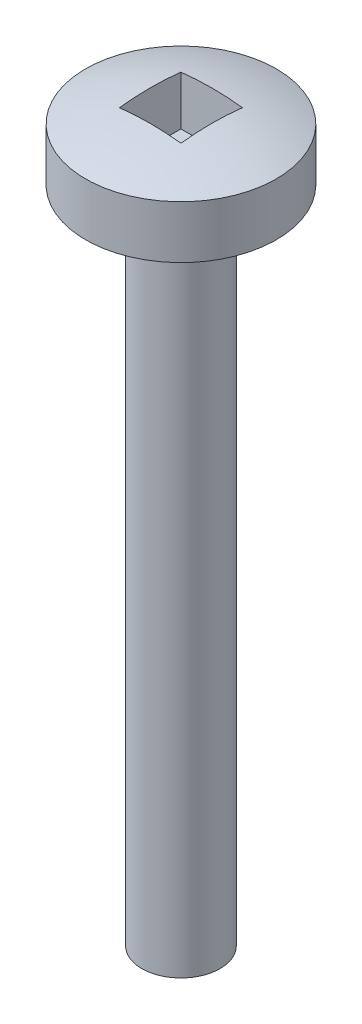
SolidWorks part; units mm, degrees
material "Cast Alloy Steel"
ref_plane "Front Plane" through (0, 0, 0) normal (0, 0, 1) x (1, 0, 0)
ref_plane "Top Plane" through (0, 0, 0) normal (0, 1, 0) x (1, 0, 0)
ref_plane "Right Plane" through (0, 0, 0) normal (1, 0, 0) x (0, 0, -1)
sketch "Sketch1" plane through (0, 0, 0) normal (0, 1, 0) x (1, 0, 0)
  circle A0 centre (0, 0) radius 1.1303
  dimension "D1" = 2.2606
extrude "threads" add sketch "Sketch1" against normal blind 19.05
sketch "Sketch2" plane through (0, 0, 0) normal (0, 1, 0) x (1, 0, 0)
  circle A0 centre (0, 0) radius 2.7559
  dimension "D1" = 5.5118
extrude "Head" add sketch "Sketch2" along normal blind 1.524
dome "HeadDome" faces to dome 1 distance 0.508 reverse direction no elliptical dome no face at (0, 1.524, 2.7559) parameters "D1"=0.508
ref_plane "DriverPlane" through (0, 2.032, 0) normal (0, 1, 0) x (1, 0, 0)
sketch "Sketch3" plane through (0, 2.032, 0) normal (0, 1, 0) x (1, 0, 0)
  line L1 (-0.889, -0.889) -> (0.889, -0.889)
  line L2 (-0.889, -0.889) -> (-0.889, 0.889)
  line L3 (-0.889, 0.889) -> (0.889, 0.889)
  line L4 (0.889, -0.889) -> (0.889, 0.889)
  line L5 (-0.889, -0.889) -> (0.889, 0.889) construction
  line L6 (-0.889, 0.889) -> (0.889, -0.889) construction
  point P0 (0, 0)
  dimension "D1" = 1.778
extrude "Driver" cut sketch "Sketch3" against normal blind 1.524
